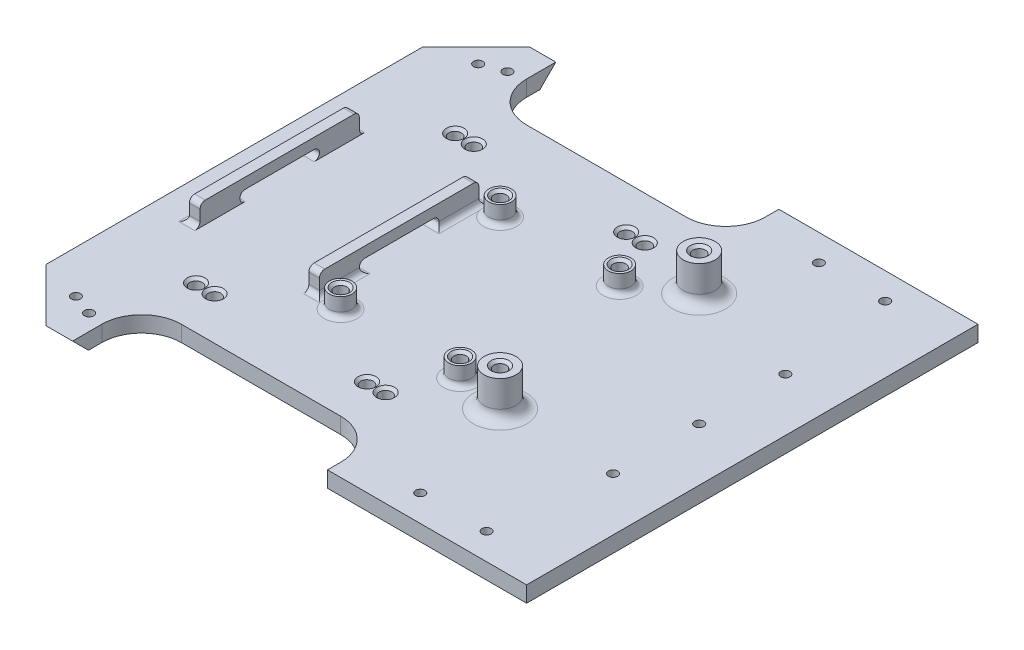
SolidWorks part; units mm, degrees
material "ABS"
ref_plane "Front Plane" through (0, 0, 0) normal (0, 0, 1) x (1, 0, 0)
ref_plane "Top Plane" through (0, 0, 0) normal (0, 1, 0) x (1, 0, 0)
ref_plane "Right Plane" through (0, 0, 0) normal (1, 0, 0) x (0, 0, -1)
sketch "Sketch1" plane through (0, 0, 0) normal (0, 1, 0) x (1, 0, 0)
  line L1 (-97.5, 85) -> (97.5, 85)
  line L2 (-97.5, 85) -> (-97.5, -85)
  line L3 (-97.5, -85) -> (97.5, -85)
  line L4 (97.5, 85) -> (97.5, -85)
  line L5 (-97.5, 85) -> (97.5, -85) construction
  line L6 (-97.5, -85) -> (97.5, 85) construction
  point P0 (0, 0)
  dimension "D1" = 195
  dimension "D2" = 170
extrude "Boss-Extrude1" add sketch "Sketch1" along normal blind 6
sketch "Sketch2" plane through (0, 6, 0) normal (0, 1, 0) x (1, 0, 0)
  line L0 (-97.5, -85) -> (-67.5, -85) construction
  line L1 (-97.5, -85) -> (97.5, -85) construction
  line L2 (0, 0) -> (-97.5, 0) construction
  line L3 (-67.5, -85) -> (22.5, -85)
  line L4 (-67.5, -85) -> (-67.5, -65)
  line L5 (-67.5, -65) -> (22.5, -65)
  line L6 (22.5, -85) -> (22.5, -65)
  line L7 (-97.5, 85) -> (-97.5, -85) construction
  line L8 (-67.5, 65) -> (22.5, 65)
  line L9 (22.5, 85) -> (22.5, 65)
  line L10 (-67.5, 85) -> (22.5, 85)
  line L11 (-67.5, 85) -> (-67.5, 65)
  dimension "D1" = 30
  dimension "D2" = 90
  dimension "D3" = 20
extrude "Cut-Extrude1" cut sketch "Sketch2" against normal through all
fillet "Fillet1" radius 15 4 edges at (22.5, 3, -65) (-67.5, 3, -65) (-67.5, 3, 65) (22.5, 3, 65)
sketch "Sketch3" plane through (0, 6, 0) normal (0, 1, 0) x (1, 0, 0)
  line L0 (0, 0) -> (-97.5, 0) construction
  line L1 (-67.5, 85) -> (-97.5, 85)
  line L2 (-67.5, 85) -> (-67.5, 91)
  line L3 (-67.5, 91) -> (-97.5, 91)
  line L4 (-97.5, 85) -> (-97.5, 91)
  line L5 (-97.5, 85) -> (-97.5, -85) construction
  line L6 (-67.5, -91) -> (-97.5, -91)
  line L7 (-97.5, -85) -> (-97.5, -91)
  line L8 (-67.5, -85) -> (-97.5, -85)
  line L9 (-67.5, -85) -> (-67.5, -91)
  dimension "D1" = 6
extrude "Boss-Extrude2" add sketch "Sketch3" against normal up to surface (6 mm away) up to face at (-16.875, 0, 0)
chamfer "Chamfer1" distance 20 angle 45 2 edges at (-97.5, 3, 91) (-97.5, 3, -91)
sketch "Sketch4" plane through (0, 6, 0) normal (0, 1, 0) x (1, 0, 0)
  line L0 (-67.5, 91) -> (-67.5, 80) construction
  line L1 (-67.5, 91.1) -> (-88.5, 91.1) construction
  line L2 (-67.5, 91.1) -> (-67.5, 68.1) construction
  line L3 (-67.5, 68.1) -> (-88.5, 68.1) construction
  line L4 (-88.5, 91.1) -> (-88.5, 68.1) construction
  line L5 (-81.5, 75.7667) -> (-73.5, 75.7667) construction
  line L6 (-73.5, 75.7667) -> (-73.5, 78.7667) construction
  line L7 (-88.5, 68.1) -> (-81.5, 75.7667) construction
  line L8 (-81.5, 75.7667) -> (-74.5, 83.4333) construction
  line L9 (-74.5, 83.4333) -> (-67.5, 91.1) construction
  line L10 (-97.5, 0) -> (0, 0) construction
  line L11 (-97.5, 71) -> (-97.5, -71) construction
  line L12 (-67.5, 91) -> (-77.5, 91) construction
  circle A0 centre (-81.5, 75.7667) radius 1.75
  circle A1 centre (-74.5, 83.4333) radius 1.75 construction
  circle A2 centre (-74.5, -83.4333) radius 1.75 construction
  circle A3 centre (-81.5, -75.7667) radius 1.75
  circle A6 centre (-73.5, 78.7667) radius 1.75
  circle A7 centre (-73.5, -78.7667) radius 1.75
  dimension "D4" = 3.5
  dimension "D5" = 3.5
  dimension "D6" = 3
  dimension "D8" = 3.5
  dimension "D1" = 23
  dimension "D2" = 21
  dimension "D3" = 0.1
  dimension "D7" = 8
extrude "Cut-Extrude2" cut sketch "Sketch4" against normal through all
sketch "Sketch7" plane through (0, 0, 0) normal (0, -1, 0) x (1, 0, 0)
  line L0 (97.5, 85) -> (97.5, -85) construction
  line L1 (22.5, 85.1) -> (97.5, 85.1) construction
  line L2 (22.5, 85.1) -> (22.5, 65) construction
  line L3 (22.5, 65) -> (97.5, 65) construction
  line L4 (97.5, 85.1) -> (97.5, 65) construction
  line L5 (22.5, 85) -> (22.5, 80) construction
  line L6 (22.5, 85) -> (97.5, 85) construction
  line L7 (22.5, 75.05) -> (47.5, 75.05) construction
  line L8 (47.5, 75.05) -> (72.5, 75.05) construction
  line L9 (72.5, 75.05) -> (97.5, 75.05) construction
  line L10 (0, 0) -> (97.5, 0) construction
  circle A0 centre (47.5, 75.05) radius 1.75
  circle A1 centre (72.5, 75.05) radius 1.75
  circle A2 centre (72.5, -75.05) radius 1.75
  circle A3 centre (47.5, -75.05) radius 1.75
  dimension "D3" = 3.5
  dimension "D4" = 3.5
  dimension "D1" = 0.1
  dimension "D2" = 20.1
extrude "Cut-Extrude5" cut sketch "Sketch7" against normal through all
sketch "Sketch8" plane through (0, 0, 0) normal (0, -1, 0) x (1, 0, 0)
  line L0 (97.5, 0) -> (57.5, 0) construction
  line L1 (97.5, 85) -> (97.5, -85) construction
  line L2 (77.5, 64.9) -> (77.5, 32.45) construction
  line L3 (57.5, 64.9) -> (97.5, 64.9) construction
  line L4 (57.5, 64.9) -> (57.5, -64.9) construction
  line L5 (57.5, -64.9) -> (97.5, -64.9) construction
  line L6 (97.5, 64.9) -> (97.5, -64.9) construction
  line L7 (57.5, 64.9) -> (97.5, -64.9) construction
  line L8 (57.5, -64.9) -> (97.5, 64.9) construction
  line L9 (77.5, 32.45) -> (77.5, 0) construction
  line L10 (77.5, 0) -> (77.5, -32.45) construction
  line L11 (77.5, -32.45) -> (77.5, -64.9) construction
  circle A0 centre (77.5, 32.45) radius 1.75
  circle A1 centre (77.5, 0) radius 1.75
  circle A2 centre (77.5, -32.45) radius 1.75
  point P5 (77.5, 0)
  dimension "D3" = 3.5
  dimension "D4" = 3.5
  dimension "D5" = 3.5
  dimension "D1" = 40
  dimension "D2" = 129.8
extrude "Cut-Extrude6" cut sketch "Sketch8" against normal through all
sketch "Sketch6" plane through (0, 0, 0) normal (0, -1, 0) x (1, 0, 0)
  line L0 (0, 0) -> (-97.5, 0) construction
  line L1 (-97.5, -71) -> (-97.5, 71) construction
  circle A1 centre (-81.5, 75.7667) radius 3.5
  circle A3 centre (-81.5, -75.7667) radius 3.5
  circle A4 centre (47.5, 75.05) radius 3.5
  circle A5 centre (72.5, 75.05) radius 3.5
  circle A6 centre (47.5, -75.05) radius 3.5
  circle A7 centre (72.5, -75.05) radius 3.5
  circle A8 centre (77.5, 32.45) radius 3.5
  circle A9 centre (77.5, 0) radius 3.5
  circle A10 centre (77.5, -32.45) radius 3.5
  circle A11 centre (-73.5, 78.7667) radius 3.5
  circle A12 centre (-73.5, -78.7667) radius 3.5
  dimension "D1" = 7
  dimension "D2" = 7
  dimension "D3" = 7
  dimension "D4" = 7
  dimension "D5" = 7
  dimension "D6" = 7
  dimension "D7" = 7
extrude "Cut-Extrude4" cut sketch "Sketch6" against normal blind 3
chamfer "Chamfer3" distance 6 angle 45 2 edges at (-72.5, 0, -91) (-72.5, 0, 91)
sketch "Sketch9" plane through (0, 6, 0) normal (0, 1, 0) x (1, 0, 0)
  line L0 (8.2, 85) -> (8.2, 48.8) construction
  line L1 (97.5, 85) -> (22.5, 85) construction
  line L2 (8.2, 48.8) -> (8.2, -48.8) construction
  line L3 (8.2, -48.8) -> (8.2, -85) construction
  line L4 (22.5, -85) -> (97.5, -85) construction
  line L5 (8.2, 48.8) -> (-63.2, 48.8) construction
  line L6 (-63.2, 48.8) -> (-63.2, -48.8) construction
  line L7 (-63.2, -48.8) -> (8.2, -48.8) construction
  line L8 (97.5, -85) -> (97.5, 85) construction
  circle A0 centre (8.2, 48.8) radius 2.35
  circle A1 centre (8.2, -48.8) radius 2.35
  circle A2 centre (-63.2, 48.8) radius 2.35
  circle A3 centre (-63.2, -48.8) radius 2.35
  circle A4 centre (-56.2, 48.8) radius 2.35
  circle A5 centre (1.2, 48.8) radius 2.35
  circle A6 centre (1.2, -48.8) radius 2.35
  circle A7 centre (-56.2, -48.8) radius 2.35
  dimension "D2" = 4.7
  dimension "D3" = 4.7
  dimension "D5" = 4.7
  dimension "D6" = 4.7
  dimension "D12" = 4.7
  dimension "D13" = 4.7
  dimension "D14" = 4.7
  dimension "D15" = 4.7
  dimension "D1" = 97.6
  dimension "D4" = 71.4
  dimension "D7" = 89.3
  dimension "D8" = 7
  dimension "D9" = 7
  dimension "D10" = 7
  dimension "D11" = 7
extrude "Cut-Extrude7" cut sketch "Sketch9" against normal blind 4.5
chamfer "Chamfer4" distance 1 angle 45 8 edges at (8.2, 6, -46.45) (1.2, 6, -46.45) (-56.2, 6, -46.45) (-63.2, 6, -46.45) (8.2, 6, 51.15) (1.2, 6, 51.15) (-56.2, 6, 51.15) (-63.2, 6, 51.15)
sketch "Sketch10" plane through (0, 6, 0) normal (0, 1, 0) x (1, 0, 0)
  line L0 (35, 42.5) -> (35, -32.5) construction
  line L1 (97.5, -85) -> (97.5, 85) construction
  line L2 (35, 42.5) -> (35, 85) construction
  line L3 (97.5, 85) -> (22.5, 85) construction
  line L4 (35, -32.5) -> (35, -85) construction
  line L6 (22.5, -85) -> (97.5, -85) construction
  circle A0 centre (35, 42.5) radius 6
  circle A1 centre (35, -32.5) radius 6
  dimension "D3" = 12
  dimension "D4" = 12
  dimension "D6" = 52.5
  dimension "D1" = 62.5
  dimension "D2" = 75
extrude "Boss-Extrude3" add sketch "Sketch10" along normal blind 14
sketch "Sketch11" plane through (0, 20, 0) normal (0, 1, 0) x (1, 0, 0)
  circle A0 centre (35, 42.5) radius 2.35
  circle A1 centre (35, -32.5) radius 2.35
  dimension "D1" = 4.7
  dimension "D2" = 4.7
extrude "Cut-Extrude8" cut sketch "Sketch11" against normal blind 9
fillet "Fillet2" radius 4 2 edges at (35, 6, -36.5) (35, 6, 38.5)
sketch "Sketch12" plane through (0, 6, 0) normal (0, 1, 0) x (1, 0, 0)
  line L0 (-9.5985, -30.04) -> (-9.5985, -65) construction
  line L1 (-27.5, 30.04) -> (17.5, 30.04) construction
  line L2 (-27.5, 30.04) -> (-27.5, -30.04) construction
  line L3 (-27.5, -30.04) -> (17.5, -30.04) construction
  line L4 (17.5, 30.04) -> (17.5, -30.04) construction
  line L5 (7.5, -65) -> (-52.5, -65) construction
  line L6 (-9.5985, 30.04) -> (-9.5985, 65) construction
  line L7 (-52.5, 65) -> (7.5, 65) construction
  line L8 (97.5, -85) -> (97.5, 85) construction
  circle A0 centre (-27.5, 30.04) radius 4.25
  circle A1 centre (17.5, 30.04) radius 4.25
  circle A2 centre (17.5, -30.04) radius 4.25
  circle A3 centre (-27.5, -30.04) radius 4.25
  dimension "D3" = 8.5
  dimension "D4" = 8.5
  dimension "D5" = 8.5
  dimension "D6" = 8.5
  dimension "D1" = 60.08
  dimension "D2" = 45
  dimension "D7" = 80
extrude "Boss-Extrude4" add sketch "Sketch12" along normal blind 7
sketch "Sketch13" plane through (0, 13, 0) normal (0, 1, 0) x (1, 0, 0)
  circle A0 centre (-27.5, 30.04) radius 2.35
  circle A1 centre (17.5, 30.04) radius 2.35
  circle A2 centre (-27.5, -30.04) radius 2.35
  circle A3 centre (17.5, -30.04) radius 2.35
  dimension "D1" = 4.7
  dimension "D2" = 4.7
  dimension "D3" = 4.7
  dimension "D4" = 4.7
extrude "Cut-Extrude9" cut sketch "Sketch13" against normal blind 10
fillet "Fillet3" radius 2 4 edges at (-27.5, 6, -25.79) (17.5, 6, -25.79) (17.5, 6, 34.29) (-27.5, 6, 34.29)
chamfer "Chamfer5" distance 1 angle 45 6 edges at (17.5, 13, -27.69) (17.5, 13, 32.39) (-27.5, 13, 32.39) (-27.5, 13, -27.69) (35, 20, -40.15) (35, 20, 34.85)
sketch "Sketch14" plane through (0, 6, 0) normal (0, 1, 0) x (1, 0, 0)
  line L0 (-97.5, 71) -> (-97.5, -71) construction
  line L1 (-84.5, 30) -> (-80.5, 30)
  line L2 (-84.5, 30) -> (-84.5, -30)
  line L3 (-84.5, -30) -> (-80.5, -30)
  line L4 (-80.5, 30) -> (-80.5, -30)
  line L5 (-39.5, 30) -> (-35.5, 30)
  line L6 (-39.5, 30) -> (-39.5, -30)
  line L7 (-39.5, -30) -> (-35.5, -30)
  line L8 (-35.5, 30) -> (-35.5, -30)
  line L9 (-37.5, -30) -> (-37.5, -65) construction
  line L10 (7.5, -65) -> (-52.5, -65) construction
  line L11 (-37.5, 30) -> (-37.5, 65) construction
  line L12 (-52.5, 65) -> (7.5, 65) construction
  dimension "D1" = 4
  dimension "D2" = 4
  dimension "D3" = 41
  dimension "D4" = 13
  dimension "D5" = 60
extrude "Boss-Extrude5" add sketch "Sketch14" along normal blind 8
sketch "Sketch15" plane through (-84.5, 0, 0) normal (-1, 0, 0) x (0, 0, 1)
  line L0 (-30, 6) -> (30, 6) construction
  line L1 (-15, 6) -> (15, 6)
  line L2 (-15, 6) -> (-15, 10)
  line L3 (-15, 10) -> (15, 10)
  line L4 (15, 6) -> (15, 10)
  line L5 (-15, 8) -> (-30, 8) construction
  line L6 (-30, 14) -> (-30, 6) construction
  line L7 (15, 8) -> (30, 8) construction
  line L8 (30, 14) -> (30, 6) construction
  dimension "D1" = 30
  dimension "D2" = 4
extrude "Cut-Extrude10" cut sketch "Sketch15" against normal up to surface (49 mm away) up to face at (-35.5, 10, 0)
fillet "Fillet4" radius 2 12 edges at (-37.5, 14, 30) (-37.5, 14, -30) (-82.5, 14, 30) (-82.5, 14, -30) (-37.5, 6, -30) (-35.5, 6, -22.5) (-35.5, 6, 22.5) (-37.5, 6, 30) (-84.5, 6, 22.5) (-82.5, 6, 30) (-82.5, 6, -30) (-84.5, 6, -22.5)
fillet "Fillet6" radius 2 8 edges at (-37.5, 10, -15) (-37.5, 10, 15) (-82.5, 10, 15) (-82.5, 10, -15) (-36.5, 6, 15) (-83.5, 6, 15) (-83.5, 6, -15) (-36.5, 6, -15)
sketch "Sketch16" [suppressed] plane through (0, 6, 0) normal (0, 1, 0) x (1, 0, 0)
  line L0 (97.5, -85) -> (97.5, 85) construction
  line L2 (15.5, 8.878) -> (15.5, 34.988) construction
  line L3 (15.5, 8.878) -> (15.5, -34.988) construction
  line L4 (15.5, 34.988) -> (15.5, 65) construction
  line L5 (-52.5, 65) -> (7.5, 65) construction
  line L6 (15.5, -34.988) -> (15.5, -65) construction
  line L7 (7.5, -65) -> (-52.5, -65) construction
  circle A0 centre (15.5, 8.878) radius 4.25
  circle A1 centre (-35.2, 24.118) radius 4.25
  circle A2 centre (-36.47, -24.142) radius 4.25
  dimension "D8" = 8.5
  dimension "D9" = 8.5
  dimension "D10" = 8.5
  dimension "D1" = 51.97
  dimension "D2" = 50.7
  dimension "D3" = 15.24
  dimension "D4" = 33.02
  dimension "D5" = 82
  dimension "D6" = 26.11
  dimension "D7" = 43.866
extrude "Boss-Extrude6" [suppressed] add sketch "Sketch16" along normal blind 10
fillet "Fillet7" [suppressed] radius 2
sketch "Sketch17" [suppressed] plane through (0, 16, 0) normal (0, 1, 0) x (1, 0, 0)
  circle A0 centre (-35.2, 24.118) radius 2.35
  circle A1 centre (15.5, 8.878) radius 2.35
  circle A2 centre (-36.47, -24.142) radius 2.35
  dimension "D1" = 4.7
  dimension "D2" = 4.7
  dimension "D3" = 4.7
extrude "Cut-Extrude11" [suppressed] cut sketch "Sketch17" against normal blind 8
chamfer "Chamfer6" [suppressed] distance 1 angle 45
